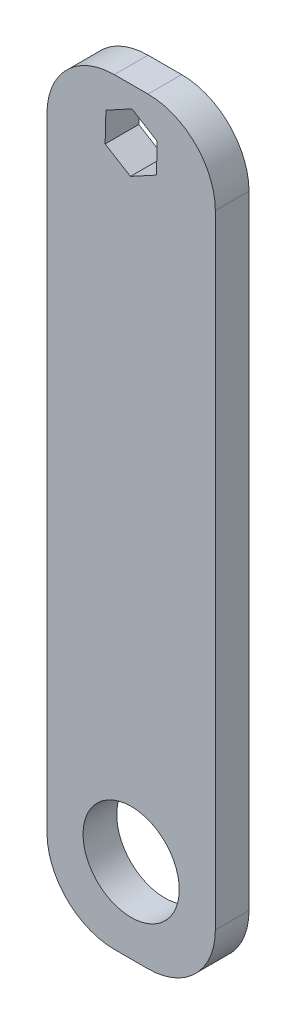
SolidWorks part; units mm, degrees
ref_plane "Front Plane" through (0, 0, 0) normal (0, 0, 1) x (1, 0, 0)
ref_plane "Top Plane" through (0, 0, 0) normal (0, 1, 0) x (1, 0, 0)
ref_plane "Right Plane" through (0, 0, 0) normal (1, 0, 0) x (0, 0, -1)
sketch "Sketch1" plane through (0, 0, 0) normal (0, 1, 0) x (1, 0, 0)
  line L1 (-25, -5) -> (25, -5)
  line L2 (-25, -5) -> (-25, 5)
  line L3 (-25, 5) -> (25, 5)
  line L4 (25, -5) -> (25, 5)
  line L5 (-25, -5) -> (25, 5) construction
  line L6 (-25, 5) -> (25, -5) construction
  point P0 (0, 0)
  dimension "D1" = 50
  dimension "D2" = 10
extrude "Boss-Extrude1" add sketch "Sketch1" along normal mid plane 225
sketch "Sketch2" plane through (0, 0, 5) normal (0, 0, 1) x (1, 0, 0)
  line L0 (0, -55) -> (0, 55) construction
  line L1 (7.5041, 92.904) -> (7.7323, 101.7007)
  line L2 (7.7323, 101.7007) -> (0.2282, 106.2967)
  line L3 (0.2282, 106.2967) -> (-7.5041, 102.096)
  line L4 (-7.5041, 102.096) -> (-7.7323, 93.2993)
  line L5 (-7.7323, 93.2993) -> (-0.2282, 88.7033)
  line L6 (-0.2282, 88.7033) -> (7.5041, 92.904)
  line L7 (-25, 112.5) -> (25, 112.5) construction
  line L8 (-25, -112.5) -> (25, -112.5) construction
  circle A0 centre (0, 97.5) radius 7.6207 construction
  circle A2 centre (0, -87.5) radius 14.2875
  point P14 (0, -87.5)
  point P15 (0, 97.5)
  point P16 (0, 97.5)
  point P24 (0, 97.5)
  dimension "D1" = 15
  dimension "D2" = 25
extrude "Cut-Extrude1" cut sketch "Sketch2" against normal blind 127
fillet "Fillet1" radius 20 4 edges at (-25, -112.5, 0) (25, -112.5, 0) (25, 112.5, 0) (-25, 112.5, 0)
sketch "Sketch4" plane through (0, 0, 0) normal (1, 0, 0) x (0, 0, -1)
  line L0 (-19.057, 97.5) -> (19.6205, 97.5) construction
  line L1 (-5, 112.5) -> (5, 112.5) construction
  dimension "D1" = 15
